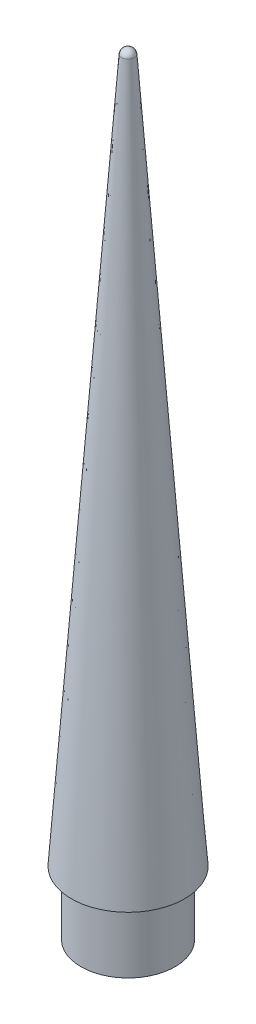
SolidWorks part; units mm, degrees
ref_plane "Front Plane" through (0, 0, 0) normal (0, 0, 1) x (1, 0, 0)
ref_plane "Top Plane" through (0, 0, 0) normal (0, 1, 0) x (1, 0, 0)
ref_plane "Right Plane" through (0, 0, 0) normal (1, 0, 0) x (0, 0, -1)
sketch "Sketch1" plane through (0, 0, 0) normal (0, 1, 0) x (1, 0, 0)
  circle A0 centre (0, 0) radius 9.398
  dimension "D1" = 18.796
extrude "Boss-Extrude1" add sketch "Sketch1" along normal blind 12.7
sketch "Sketch3" plane through (0, 0, 0) normal (1, 0, 0) x (0, 0, -1)
  line L0 (11.303, 12.7) -> (0, 170.6459)
  line L1 (0, 170.6459) -> (0, 12.7)
  line L2 (9.398, 12.7) -> (-9.398, 12.7) construction
  line L3 (0, 12.7) -> (11.303, 12.7)
  line L4 (29.083, -235.7541) -> (11.303, 12.7) construction
  line L5 (0, 152.8991) -> (1.27, 152.8991) construction
  arc A0 (1.27, 152.8991) -> (0, 154.1691) centre (0, 152.8991) ccw
  dimension "D1" = 1.27
revolve "Revolve1" add sketch "Sketch3" angle 360 about L1 region at (0, 64.1536, -3.8104) region at (0, 153.4383, -0.5388)
sketch "Sketch5" plane through (0, 0, 0) normal (0, -1, 0) x (1, 0, 0)
  point P0 (0, 0)
hole_wizard "Tap Drill for #8-32 Tap1" positions "Sketch7" profile "Sketch9" hole size "#8-32" standard "ANSI Inch"
sketch "Sketch7" plane through (0, 0, 0) normal (0, -1, 0) x (-1, 0, 0)
  point P0 (0, 0)
sketch "Sketch9" plane through (0, 0, 0) normal (1, 0, 0) x (0, 0, -1)
  line L0 (0, 0) -> (0, 11.1978)
  line L1 (0, 11.1978) -> (1.7272, 10.16)
  line L2 (1.7272, 10.16) -> (1.7272, 0)
  line L5 (1.7272, 0) -> (0, 0)
  line L10 (0, 11.1978) -> (-1.7272, 10.16) construction
  line L11 (0, -6.35) -> (0, 107.95) construction
  dimension "Hole Dia." = 3.4544
  dimension "Hole Depth" = 10.16
  dimension "Drill Angle" = 118
